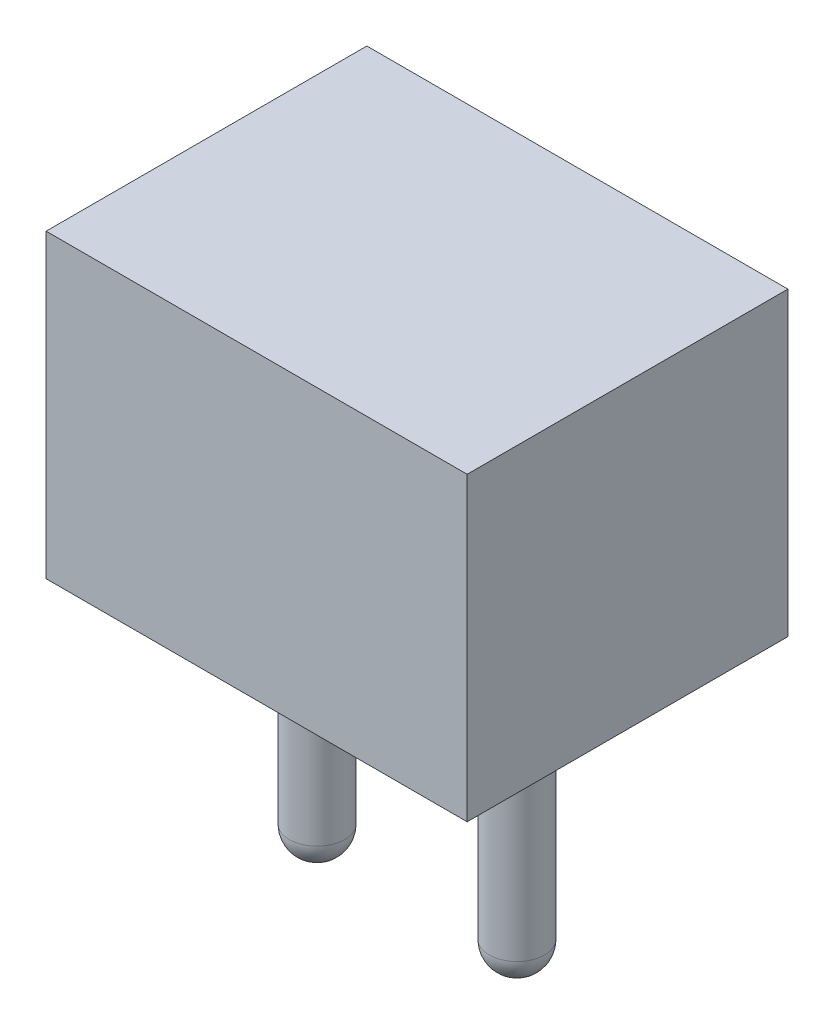
SolidWorks part; units mm, degrees
ref_plane "Front Plane" through (0, 0, 0) normal (0, 0, 1) x (1, 0, 0)
ref_plane "Top Plane" through (0, 0, 0) normal (0, 1, 0) x (1, 0, 0)
ref_plane "Right Plane" through (0, 0, 0) normal (1, 0, 0) x (0, 0, -1)
sketch "Sketch1" plane through (0, 0, 0) normal (0, 1, 0) x (1, 0, 0)
  line L0 (1.4, 0) -> (-3.93, 0) construction
  line L1 (-3.93, 2.03) -> (1.4, 2.03)
  line L2 (-3.93, 2.03) -> (-3.93, -2.03)
  line L3 (-3.93, -2.03) -> (1.4, -2.03)
  line L4 (1.4, 2.03) -> (1.4, -2.03)
  dimension "D1" = 1.4
  dimension "D2" = 4.06
  dimension "D3" = 5.33
extrude "Base-Extrude" add sketch "Sketch1" along normal blind 3.81
sketch "Sketch2" plane through (0, 0, 0) normal (0, -1, 0) x (1, 0, 0)
  line L0 (-1.265, -2.03) -> (-1.265, 2.03) construction
  line L1 (1.4, -2.03) -> (-3.93, -2.03) construction
  line L2 (-3.93, 2.03) -> (1.4, 2.03) construction
  circle A0 centre (0, 0) radius 0.35
  circle A1 centre (-2.53, 0) radius 0.35
  dimension "D1" = 0.7
extrude "Boss-Extrude1" add sketch "Sketch2" along normal blind 3
dome "Dome1" faces to dome 1 distance 0.35 reverse direction no elliptical dome no face at (0, -3, -0.35) parameters "D1"=0.35
dome "Dome2" faces to dome 1 distance 0.35 reverse direction no elliptical dome no face at (-2.53, -3, 0.35) parameters "D1"=0.35
ref_plane "Board Plane" through (0, -0.3, 0) normal (0, 1, 0) x (-1, 0, 0)
sketch "Component_Outline" plane through (0, -0.3, 0) normal (0, 1, 0) x (-1, 0, 0)
  line L1 (3.93, 2.03) -> (-1.4, 2.03)
  line L2 (3.93, 2.03) -> (3.93, -2.03)
  line L3 (3.93, -2.03) -> (-1.4, -2.03)
  line L4 (-1.4, 2.03) -> (-1.4, -2.03)
  point P6 (0, 0)
